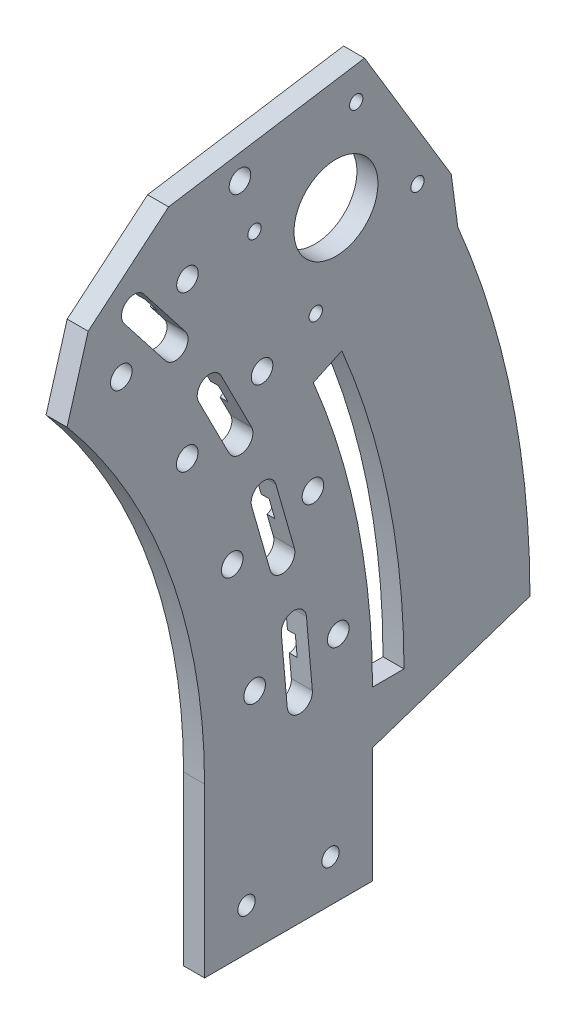
SolidWorks part; units mm, degrees
other "Markup1"
sketch "Sketch5" plane through (7.4724, -50.8, -116.7452) normal (0.7166, -0.0822, 0.6926) x (0.6913, -0.0479, -0.721)
other "Markup2"
sketch "Sketch6" plane through (7.4724, -50.8, -116.7452) normal (0.7166, -0.0822, 0.6926) x (0.6913, -0.0479, -0.721)
material "6061-T6 (SS)"
ref_plane "Front Plane" through (0, 0, 0) normal (0, 0, 1) x (1, 0, 0)
ref_plane "Top Plane" through (0, 0, 0) normal (0, 1, 0) x (1, 0, 0)
ref_plane "Right Plane" through (0, 0, 0) normal (1, 0, 0) x (0, 0, -1)
sketch "Sketch1" plane through (0, 0, 0) normal (1, 0, 0) x (0, 0, -1)
  line L0 (0, 0) -> (177.8, 0) construction
  line L1 (0, 0) -> (136.2027, 114.2876) construction
  line L2 (177.8, 0) -> (177.8, -50.8)
  line L3 (177.8, -50.8) -> (228.6, -50.8)
  line L4 (228.6, -50.8) -> (228.6, 0) construction
  line L5 (136.2027, 114.2876) -> (148.2956, 124.4347) construction
  line L6 (177.8, 0) -> (228.6, 0) construction
  line L7 (136.2027, 114.2876) -> (148.2956, 124.4347) construction
  line L8 (0, 0) -> (202.4268, 17.71) construction
  line L9 (0, 0) -> (0, 168.3639) construction
  line L10 (202.4268, 17.71) -> (208.7526, 18.2635) construction
  line L11 (0, 0) -> (200.1129, 35.2853) construction
  line L12 (0, 0) -> (196.2761, 52.592) construction
  line L13 (0, 0) -> (190.9455, 69.4985) construction
  line L14 (0, 0) -> (184.1617, 85.876) construction
  line L15 (0, 0) -> (175.9764, 101.6) construction
  line L16 (0, 0) -> (166.4517, 116.5507) construction
  line L17 (0, 0) -> (200.1129, 35.2853) construction
  line L18 (0, 0) -> (196.2761, 52.592) construction
  line L19 (208.7526, 18.2635) -> (221.4043, 19.3704) construction
  line L20 (206.3665, 36.388) -> (218.8735, 38.5933) construction
  line L21 (202.4098, 54.2355) -> (214.677, 57.5225) construction
  line L22 (196.9126, 71.6703) -> (208.8467, 76.014) construction
  line L23 (189.9168, 88.5597) -> (201.4269, 93.9269) construction
  line L24 (181.4756, 104.775) -> (192.4741, 111.125) construction
  line L25 (171.6533, 120.1929) -> (182.0565, 127.4774) construction
  line L26 (0, 0) -> (208.7526, 18.2635) construction
  line L27 (0, 0) -> (206.3665, 36.388) construction
  line L28 (177.8, -50.8) -> (177.8, -38.1) construction
  line L29 (177.8, -38.1) -> (228.6, -38.1) construction
  line L30 (0, 0) -> (42824.6192, 25807.9831) construction
  line L31 (217.5491, 131.1046) -> (204.4386, 152.8595) construction
  line L32 (217.5491, 131.1046) -> (230.6595, 109.3496) construction
  line L33 (239.304, 144.215) -> (226.1935, 165.9699)
  line L34 (239.304, 144.215) -> (252.4144, 122.4601)
  line L36 (199.1064, 161.7074) -> (226.1935, 165.9699)
  line L37 (219.3273, 92.731) -> (235.9917, 100.5017) construction
  line L38 (210.6888, 88.7028) -> (235.9917, 100.5017) construction
  line L39 (235.9917, 100.5017) -> (252.4144, 122.4601) construction
  line L40 (219.3273, 92.731) -> (210.6888, 88.7028)
  line L41 (228.6, 0) -> (238.125, 0)
  line L42 (228.6, -15.875) -> (276.225, 0)
  line L43 (252.4144, 122.4601) -> (254.4197, 107.5679)
  line L44 (228.6, -50.8) -> (228.6, -15.875)
  line L45 (217.5491, 131.1046) -> (213.0063, 112.7824) construction
  line L47 (0, 0) -> (136.2027, 114.2876) construction
  line L48 (136.2027, 114.2876) -> (142.6, 136.2343)
  line L49 (142.6, 136.2343) -> (166.9219, 156.6428)
  line L50 (166.9219, 156.6428) -> (199.1064, 161.7074)
  line L51 (211.4365, 106.451) -> (217.5491, 131.1046) construction
  line L52 (217.5491, 131.1046) -> (223.6616, 155.7581) construction
  arc A0 (177.8, 0) -> (136.2027, 114.2876) centre (0, 0) ccw
  arc A1 (228.6, 0) -> (210.6888, 88.7028) centre (0, 0) ccw
  circle A2 centre (202.4268, 17.71) radius 6.35 construction
  arc A4 (208.7526, 18.2635) -> (160.5246, 134.6961) centre (0, 0) ccw construction
  arc A5 (215.0784, 18.8169) -> (165.389, 138.7778) centre (0, 0) ccw construction
  circle A7 centre (221.4043, 19.3704) radius 6.35 construction
  circle A9 centre (200.1129, 35.2853) radius 6.35 construction
  circle A11 centre (196.2761, 52.592) radius 6.35 construction
  circle A13 centre (190.9455, 69.4985) radius 6.35 construction
  circle A15 centre (184.1617, 85.876) radius 6.35 construction
  circle A17 centre (175.9764, 101.6) radius 6.35 construction
  circle A19 centre (166.4517, 116.5507) radius 6.35 construction
  circle A21 centre (218.8735, 38.5933) radius 6.35 construction
  circle A23 centre (214.677, 57.5225) radius 6.35 construction
  circle A25 centre (208.8467, 76.014) radius 6.35 construction
  circle A27 centre (201.4269, 93.9269) radius 6.35 construction
  circle A29 centre (192.4741, 111.125) radius 6.35 construction
  circle A31 centre (182.0565, 127.4774) radius 6.35 construction
  circle A32 centre (190.5, -38.1) radius 2.6289
  circle A33 centre (215.9, -38.1) radius 2.6289
  circle A34 centre (217.5491, 131.1046) radius 12.7
  circle A36 centre (230.6595, 109.3496) radius 2.0193 construction
  arc A37 (219.3273, 92.731) -> (238.125, 0) centre (0, 0) cw
  arc A38 (254.4197, 107.5679) -> (276.225, 0) centre (0, 0) cw
  circle A41 centre (192.8955, 137.2171) radius 2.0193
  circle A42 centre (223.6616, 155.7581) radius 2.0193
  circle A45 centre (217.5491, 131.1046) radius 12.7
  circle A46 centre (242.2026, 124.992) radius 2.0193
  circle A47 centre (217.5491, 131.1046) radius 12.7
  circle A48 centre (211.4365, 106.451) radius 2.0193
  circle A49 centre (217.5491, 131.1046) radius 12.7
  point P11 (177.1234, 15.4963)
  point P24 (175.0988, 30.8746)
  point P82 (239.304, 144.215)
  point P124 (217.5491, 131.1046)
  dimension "D5" = 12.7
  dimension "D7" = 22.86
  dimension "D12" = 12.7
  dimension "D24" = 5.2578
  dimension "D25" = 5.2578
  dimension "D28" = 25.4
  dimension "D30" = 25.4
  dimension "D32" = 4.0386
  dimension "D35" = 9.525
  dimension "D43" = 4.0386
  dimension "D1" = 177.8
  dimension "D2" = 40
  dimension "D3" = 50.8
  dimension "D4" = 50.8
  dimension "D6" = 5
  dimension "D8" = 25.4
  dimension "D10" = 90
  dimension "D13" = 25.4
  dimension "D14" = 5
  dimension "D16" = 5
  dimension "D17" = 6.35
  dimension "D20" = 5
  dimension "D21" = 12.7
  dimension "D22" = 12.7
  dimension "D23" = 12.7
  dimension "D26" = 8.925
  dimension "D27" = 254
  dimension "D29" = 25.4
  dimension "D31" = 25.4
  dimension "D33" = 25.4
  dimension "D34" = 25.4
  dimension "D37" = 15.875
  dimension "D38" = 45
  dimension "D41" = 12.7
  dimension "D42" = 31.75
  dimension "D9" = 6.35
  dimension "D36" = 38.1
  dimension "D15" = 6
  dimension "D19" = 7
  dimension "D45" = 4
extrude "Boss-Extrude1" add sketch "Sketch1" along normal blind 6.35 contours A38 L43 L34 L33 L36 L50 L49 L48 A0 L2 L3 L44 L42 A48 A46 A42 A41 A34 A33 A32 region at (0, 62.7809, -209.1921)
sketch "Sketch7" plane through (0, 0, 0) normal (0, 0, 1) x (1, 0, 0)
  line L0 (0, 0) -> (50000, 0) construction
sketch "Sketch8" plane through (0, 0, 0) normal (-1, 0, 0) x (0, 0, 1)
  line L0 (0, 0) -> (-218.2414, 19.0936) construction
  line L1 (0, 0) -> (-81.6847, 0) construction
  line L2 (0, 0) -> (-210.5884, 60.3853) construction
  line L3 (0, 0) -> (-195.1973, 99.458) construction
  line L4 (0, 0) -> (-172.6335, 134.876) construction
  line L5 (-201.0352, 27.7871) -> (-202.8062, 7.5444)
  line L6 (-192.0396, 65.6359) -> (-197.6405, 46.1031)
  line L7 (0, 0) -> (-192.938, 16.8799) construction
  line L8 (0, 0) -> (-186.1724, 53.3841) construction
  line L9 (-202.8062, 7.5444) -> (-201.0352, 27.7871) construction
  line L10 (-201.0352, 27.7871) -> (-208.6262, 28.4512) construction
  line L11 (-208.6262, 28.4512) -> (-210.3972, 8.2086)
  line L12 (-210.3972, 8.2086) -> (-202.8062, 7.5444) construction
  line L13 (-204.9653, 48.2034) -> (-197.6405, 46.1031) construction
  line L15 (-192.0396, 65.6359) -> (-199.3644, 67.7363) construction
  line L16 (-199.3644, 67.7363) -> (-204.9653, 48.2034)
  line L17 (-192.0019, 86.427) -> (-185.2124, 82.9676) construction
  line L19 (-175.9874, 101.0729) -> (-182.7768, 104.5323) construction
  line L20 (-182.7768, 104.5323) -> (-192.0019, 86.427)
  line L21 (-171.9832, 121.4748) -> (-165.9786, 116.7835) construction
  line L23 (-153.4684, 132.7958) -> (-159.473, 137.4872) construction
  line L24 (-159.473, 137.4872) -> (-171.9832, 121.4748)
  line L25 (-197.6405, 46.1031) -> (-192.0396, 65.6359) [skipped]
  line L27 (-185.2124, 82.9676) -> (-175.9874, 101.0729) [skipped]
  line L28 (-175.9874, 101.0729) -> (-185.2124, 82.9676)
  line L30 (-165.9786, 116.7835) -> (-153.4684, 132.7958) [skipped]
  line L34 (-165.9786, 116.7835) -> (-153.4684, 132.7958)
  circle A0 centre (-218.2414, 19.0936) radius 3.2639
  arc A1 (-208.6262, 28.4512) -> (-201.0352, 27.7871) centre (-204.8307, 28.1192) cw
  circle A2 centre (-192.938, 16.8799) radius 3.2639
  circle A3 centre (-210.5884, 60.3853) radius 3.2639
  circle A4 centre (-186.1724, 53.3841) radius 3.2639
  circle A5 centre (-195.1973, 99.458) radius 3.2639
  circle A6 centre (-172.5657, 87.9266) radius 3.2639
  circle A7 centre (-172.6335, 134.876) radius 3.2639
  circle A8 centre (-152.618, 119.2382) radius 3.2639
  arc A13 (-210.3972, 8.2086) -> (-202.8062, 7.5444) centre (-206.6017, 7.8765) ccw
  arc A14 (-204.9653, 48.2034) -> (-197.6405, 46.1031) centre (-201.3029, 47.1532) ccw
  arc A15 (-199.3644, 67.7363) -> (-192.0396, 65.6359) centre (-195.702, 66.6861) cw
  arc A16 (-192.0019, 86.427) -> (-185.2124, 82.9676) centre (-188.6072, 84.6973) ccw
  arc A17 (-182.7768, 104.5323) -> (-175.9874, 101.0729) centre (-179.3821, 102.8026) cw
  arc A18 (-159.473, 137.4872) -> (-153.4684, 132.7958) centre (-156.4707, 135.1415) cw
  arc A19 (-171.9832, 121.4748) -> (-165.9786, 116.7835) centre (-168.9809, 119.1291) ccw
  dimension "D3" = 6.5278
  dimension "D4" = 6.5278
  dimension "D1" = 219.075
  dimension "D2" = 5
  dimension "D5" = 25.4
  dimension "D7" = 11
  dimension "D8" = 20.32
  dimension "D9" = 7.62
  dimension "D10" = 10.16
  dimension "D11" = 9.017
  dimension "D6" = 4
extrude "Cut-Extrude1" cut sketch "Sketch8" against normal through all
sketch "Sketch9" plane through (0, 18.3299, -209.5117) normal (-1, 0, 0) x (0, -0.0872, 0.9962)
  line L0 (0, 0) -> (-2.3812, 0) construction
  line L1 (0, 10.16) -> (0, -10.16) construction
  line L3 (7.62, -10.16) -> (7.62, 10.16) construction
  circle A1 centre (0, 0) radius 3.175
  circle A2 centre (7.62, 0) radius 3.175
  dimension "D1" = 6.35
  dimension "D3" = 6.35
  dimension "D2" = 2.3812
extrude "Cut-Extrude2" cut sketch "Sketch9" against normal blind 2.3813 and the other way blind 10.033
pattern_circular "CirPattern1" count 4 every 11 about axis through (0, 0, 0) along (1, 0, 0) of "Cut-Extrude2"
sketch "Sketch10" plane through (0, 0, 0) normal (-1, 0, 0) x (0, 0, 1)
  line L0 (0, 0) -> (-188.5123, 152.6542) construction
  line L1 (0, 0) -> (-65.3997, 0) construction
  circle A0 centre (-188.5123, 152.6542) radius 3.2639
  dimension "D1" = 6.5278
  dimension "D2" = 242.57
  dimension "D3" = 39
extrude "Cut-Extrude3" cut sketch "Sketch10" against normal through all
